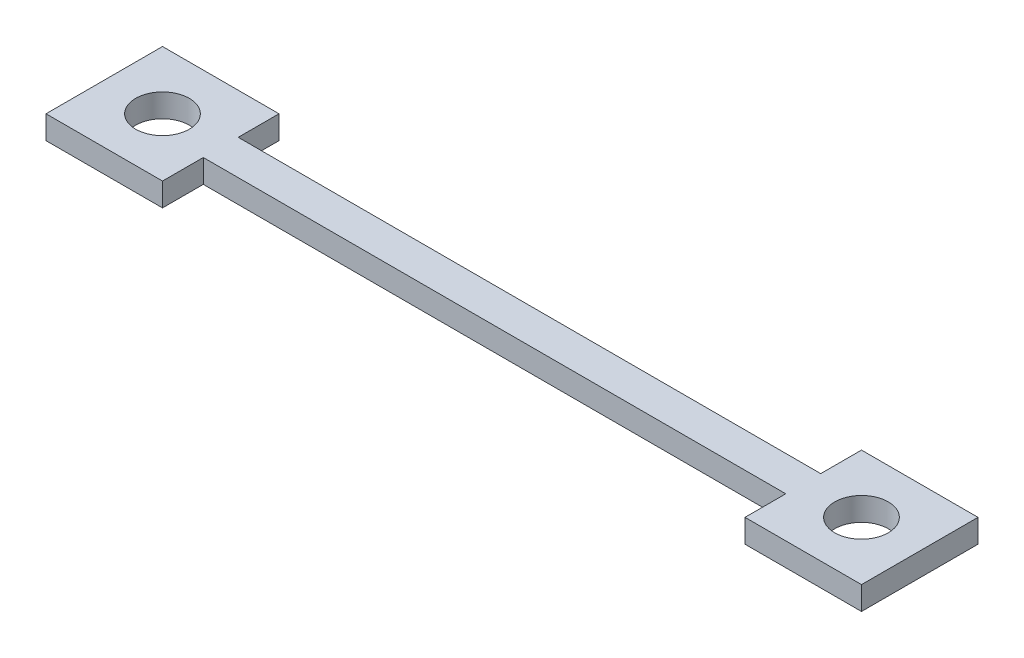
SolidWorks part; units mm, degrees
material "Commercially Pure CP-Ti UNS R50400 (SS)"
ref_plane "Front Plane" through (0, 0, 0) normal (0, 0, 1) x (1, 0, 0)
ref_plane "Top Plane" through (0, 0, 0) normal (0, 1, 0) x (1, 0, 0)
ref_plane "Right Plane" through (0, 0, 0) normal (1, 0, 0) x (0, 0, -1)
sketch "Sketch1" plane through (0, 0, 0) normal (0, 1, 0) x (1, 0, 0)
  line L0 (-41.424, -10.2833) -> (-41.424, -12.5058)
  line L1 (-47.774, -12.5058) -> (-41.424, -12.5058)
  line L2 (-47.774, -12.5058) -> (-47.774, -6.1558)
  line L3 (-47.774, -6.1558) -> (-41.424, -6.1558)
  line L4 (-3.324, -12.5058) -> (-3.324, -6.1558)
  line L7 (-41.424, -10.2833) -> (-9.674, -10.2833)
  line L9 (-41.424, -8.3783) -> (-9.674, -8.3783)
  line L13 (-41.424, -8.3783) -> (-41.424, -6.1558)
  line L14 (-9.674, -8.3783) -> (-9.674, -6.1558)
  line L15 (-9.674, -10.2833) -> (-9.674, -12.5058)
  line L16 (-9.674, -6.1558) -> (-3.324, -6.1558)
  line L17 (-9.674, -12.5058) -> (-3.324, -12.5058)
  point P0 (0, 0)
  point P6 (0, 0)
  dimension "D1" = 44.45
  dimension "D2" = 6.35
  dimension "D3" = 6.35
  dimension "D4" = 1.905
extrude "Boss-Extrude1" add sketch "Sketch1" along normal mid plane 1.27
hole_wizard "#97 (0.0059) Diameter Hole1" positions "Sketch4" profile "Sketch3" hole size "#97" standard "Ansi Inch" end condition through all
sketch "Sketch4" plane through (0, 0.635, 0) normal (0, 1, 0) x (-1, 0, 0)
  line L0 (47.774, 12.5058) -> (41.424, 6.1558) construction
  point P0 (44.599, 9.3308)
sketch "Sketch3" plane through (-44.599, 0.635, 9.3308) normal (1, 0, 0) x (0, 0, 1)
  line L0 (0, 0) -> (0, 1.27)
  line L1 (0, 1.27) -> (1.4605, 1.27)
  line L2 (1.4605, 1.27) -> (1.4605, 0)
  line L5 (1.4605, 0) -> (0, 0)
  line L11 (0, -6.35) -> (0, 107.95) construction
  dimension "Thru Hole Dia." = 2.921
  dimension "Thru Hole Depth" = 1.27
ref_plane "Plane1" through (-25.549, 0, 0) normal (1, 0, 0) x (0, 0, -1)
mirror "Mirror1" about plane through (-25.549, 0, 0) normal (1, 0, 0) of "#97 (0.0059) Diameter Hole1"
